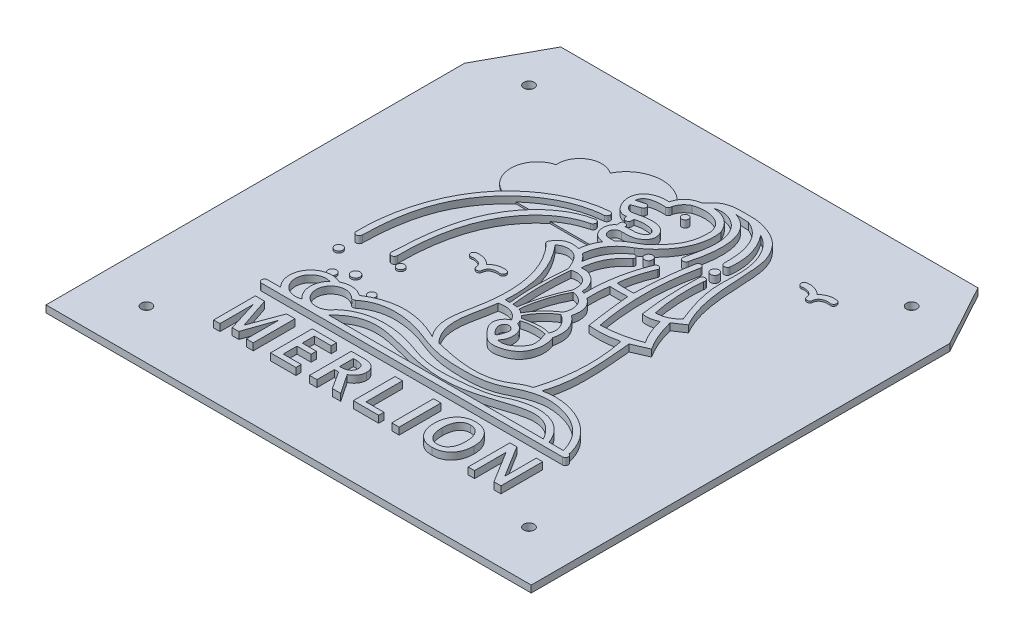
SolidWorks part; units mm, degrees
ref_plane "Front Plane" through (0, 0, 0) normal (0, 0, 1) x (1, 0, 0)
ref_plane "Top Plane" through (0, 0, 0) normal (0, 1, 0) x (1, 0, 0)
ref_plane "Right Plane" through (0, 0, 0) normal (1, 0, 0) x (0, 0, -1)
sketch "Sketch2" plane through (0, 0, 0) normal (0, 1, 0) x (1, 0, 0)
  line L0 (-69.75, 120.33) -> (-69.75, 0)
  line L1 (-69.75, 0) -> (69.75, 0)
  line L2 (69.75, 0) -> (69.75, 120.33)
  line L3 (69.75, 120.33) -> (59.98, 138.2123)
  line L4 (59.98, 138.2123) -> (-59.98, 138.2123)
  line L5 (-59.98, 138.2123) -> (-69.75, 120.33)
  line L6 (-55, 124.11) -> (-55, 14.11) construction
  line L7 (-55, 14.11) -> (55, 14.11) construction
  line L8 (55, 14.11) -> (55, 124.11) construction
  line L9 (55, 124.11) -> (-55, 124.11) construction
  line L10 (0, 14.11) -> (0, 0) construction
  circle A0 centre (-55, 124.11) radius 1.5
  circle A1 centre (55, 124.11) radius 1.5
  circle A2 centre (55, 14.11) radius 1.5
  circle A3 centre (-55, 14.11) radius 1.5
  point P6 (0, 0)
  dimension "D6" = 3
  dimension "D1" = 139.5
  dimension "D2" = 120.33
  dimension "D3" = 118.65
  dimension "D4" = 118.65
  dimension "D5" = 119.96
  dimension "D7" = 110
  dimension "D8" = 110
  dimension "D9" = 14.11
extrude "Boss-Extrude1" add sketch "Sketch2" along normal blind 2
sketch "Sketch4" plane through (0, 2, 0) normal (0, 1, 0) x (1, 0, 0)
  text T0 "BOROBUDUR" font "Lucida Sans Unicode" height 13
  point P1 (-42.6909, 27.0637)
  point P2 (-44.2843, 26.8361)
extrude "Boss-Extrude3" [suppressed] add sketch "Sketch4" along normal blind 2
sketch "Sketch7" plane through (0, 2, 0) normal (0, 1, 0) x (1, 0, 0)
  line L0 (-1201.3468, -665.5379) -> (-197.3468, -665.5379) construction
  line L1 (192.2315, 826.584) -> (1196.2315, 826.584) construction
  line L2 (44.3003, 34.3883) -> (-42.1624, 34.3883)
  line L3 (-42.1624, 36.1128) -> (-38.4101, 36.1128)
  line L4 (-24.5761, 36.1128) -> (37.1275, 36.1128)
  line L5 (38.7521, 36.1128) -> (42.84, 36.1128)
  line L6 (-3.6083, 95.618) -> (-1.8162, 95.618)
  line L7 (8.8644, 119.6853) -> (12.6966, 119.5166)
  arc A0 (-9.9574, 100.5454) -> (-10.1272, 102.3547) centre (-9.9588, 101.4579) ccw
  arc A1 (-41.4476, 60.8648) -> (-39.6862, 60.8648) centre (-40.5669, 60.8648) ccw
  arc A2 (-9.8077, 96.5277) -> (-10.1913, 98.2839) centre (-9.9451, 97.4177) ccw
  arc A3 (-31.2299, 60.8454) -> (-29.4923, 60.7921) centre (-30.3624, 60.7758) ccw
  arc A5 (-32.8244, 44.6802) -> (-32.4376, 36.2676) centre (-28.5345, 40.6623) ccw
  arc A6 (-32.8244, 44.6802) -> (-32.4376, 36.2676) centre (-34.0547, 40.4085) ccw
  arc A7 (-25.9183, 43.968) -> (-24.9659, 38.4179) centre (-28.5345, 40.6623) ccw
  arc A8 (-42.1624, 36.1128) -> (-42.1624, 34.3883) centre (-42.1624, 35.2506) ccw
  arc A9 (44.3003, 34.3883) -> (44.5437, 36.0777) centre (44.3003, 35.2506) ccw
  arc A10 (-25.0696, 45.4102) -> (-31.279, 45.8599) centre (-28.5345, 40.6623) ccw
  arc A11 (-31.279, 45.8599) -> (-38.4101, 36.1128) centre (-34.0547, 40.4085) ccw
  arc A12 (-3.128, 111.4372) -> (-2.2531, 112.4271) centre (-3.0754, 112.2722) ccw
  arc A13 (-6.7924, 109.4078) -> (-6.3281, 107.7759) centre (-6.5603, 108.5919) cw
  arc A14 (12.0547, 101.618) -> (13.7739, 101.118) centre (12.9, 101.3189) ccw
  arc A15 (19.3136, 105.971) -> (21.1274, 105.8666) centre (20.2204, 105.9169) ccw
  circle A16 centre (2.3013, 111.7181) radius 0.9837
  circle A17 centre (7.065, 96.4138) radius 1.1652
  circle A18 centre (20.2204, 102.2849) radius 1.1751
  arc A19 (5.0875, 93.854) -> (3.8629, 94.9403) centre (4.425, 94.3406) ccw
  arc A20 (11.2355, 94.4528) -> (9.7612, 95.2234) centre (10.5518, 94.9403) ccw
  arc A21 (17.1346, 101.1863) -> (15.4382, 101.5027) centre (16.2926, 101.3778) ccw
  arc A22 (20.9973, 98.2839) -> (19.3636, 98.6157) centre (20.2204, 98.6465) ccw
  spline S0 degree 3 poles (-9.9588, 102.3704) (-18.6465, 101.5875) (-36.2323, 91.1471) (-41.6505, 71.1239) (-41.4476, 60.8648) knots 0 0 0 0 0.451584 1 1 1 1
  spline S1 degree 3 poles (-39.6862, 60.8648) (-39.5972, 67.3837) (-37.455, 85.8607) (-21.5995, 99.5998) (-9.8077, 100.558) knots 0 0 0 0 0.362724 1 1 1 1
  spline S2 degree 3 poles (-31.2327, 60.7758) (-30.8994, 69.13) (-29.556, 85.1596) (-17.0075, 96.9409) (-10.1913, 98.2839) knots 0 0 0 0 0.551911 1 1 1 1
  spline S3 degree 3 poles (-9.8077, 96.5277) (-16.2307, 94.9492) (-27.5198, 84.0891) (-29.568, 68.812) (-29.4922, 60.7758) knots 0 0 0 0 0.442158 1 1 1 1
  spline S4 degree 3 poles (-26.0695, 37.2424) (-21.5331, 42.7418) (-12.2233, 43.2325) (0.2095, 38.4079) (5.0793, 37.912) (21.0184, 39.3159) (20.0588, 41.0511) (31.0608, 43.7308) (36.8095, 41.5293) (38.7521, 36.1128) knots 0 0 0 0 0.209239 0.240528 0.334429 0.377612 0.660626 0.719916 1 1 1 1
  spline S5 degree 3 poles (-24.5761, 36.1128) (-22.9325, 37.9529) (-17.4081, 41.5272) (-7.6539, 39.3095) (1.9661, 36.5213) (12.7707, 36.1717) (24.3192, 40.3392) (33.3882, 42.7039) (37.1275, 36.1128) knots 0 0 0 0 0.115498 0.281888 0.432798 0.585218 0.767439 1 1 1 1
  spline S6 degree 2 poles (-25.0696, 45.4102) (-15.7624, 51.4204) (-4.3446, 45.6251) knots 0 0 0 1 1 1
  spline S7 degree 3 poles (-4.3446, 45.6251) (-8.0002, 50.3018) (-3.2731, 63.7943) (-4.6708, 78.3512) (-10.9267, 84.9324) knots 0 0 0 0 0.374184 1 1 1 1
  spline S8 degree 2 poles (-10.9267, 84.9324) (-11.6464, 85.2936) (-11.3916, 86.0741) knots 0 0 0 1 1 1
  spline S9 degree 2 poles (-11.3916, 86.0741) (-9.5366, 89.6845) (-5.21, 88.5802) knots 0 0 0 1 1 1
  spline S10 degree 2 poles (-3.4433, 93.735) (-4.9873, 91.3749) (-5.21, 88.5802) knots 0 0 0 1 1 1
  spline S11 degree 3 poles (-5.597, 100.0006) (-7.2855, 98.9493) (-7.2984, 94.7473) (-4.3168, 93.8483) (-3.4433, 93.735) knots 0 0 0 0 0.6762 1 1 1 1
  spline S12 degree 2 poles (-25.9183, 43.968) (-25.2496, 43.1673) (-24.4072, 43.6465) knots 0 0 0 1 1 1
  spline S13 degree 3 poles (-24.4072, 43.6465) (-22.0022, 45.6472) (-16.1415, 47.2243) (-6.3264, 45.027) (-0.4952, 41.8053) (15.7146, 41.4602) (19.5224, 44.5582) (26.0491, 46.7407) (32.7571, 46.4087) (40.8745, 43.8715) (42.84, 36.1128) knots 0 0 0 0 0.133923 0.258154 0.412619 0.501567 0.692749 0.812953 0.843678 1 1 1 1
  spline S14 degree 3 poles (-5.597, 100.0006) (-5.704, 100.3924) (-5.9698, 102.1171) (-3.8284, 101.5488) (-3.9822, 100.7065) knots 0 0 0 0 0.434244 1 1 1 1
  spline S15 degree 3 poles (-3.9822, 100.7065) (-2.6514, 100.9332) (-0.0463, 100.2599) (2.3348, 102.8556) (0.3378, 103.948) knots 0 0 0 0 0.520536 1 1 1 1
  spline S16 degree 2 poles (0.3378, 103.948) (-2.075, 104.5253) (-4.5507, 103.8172) knots 0 0 0 1 1 1
  spline S17 degree 3 poles (-6.3281, 103.5013) (-6.4115, 103.013) (-5.8594, 102.057) (-4.4292, 102.476) (-4.4559, 103.4081) (-4.5507, 103.8172) knots 0 0 0 0 0.417961 0.636874 1 1 1 1
  spline S18 degree 3 poles (-6.3281, 103.5013) (-8.4367, 102.9694) (-11.2774, 106.4974) (-10.2348, 112.4129) (-5.8343, 113.4739) (-3.8248, 113.1894) knots 0 0 0 0 0.371124 0.593458 1 1 1 1
  spline S19 degree 2 poles (-3.8248, 113.1894) (-2.8716, 117.0541) (1.2989, 117.681) knots 0 0 0 1 1 1
  spline S20 degree 3 poles (1.2989, 117.681) (3.1476, 119.8951) (5.116, 121.6799) (12.1692, 121.2827) (12.2063, 121.2856) knots 0 0 0 0 0.585988 1 1 1 1
  spline S21 degree 3 poles (12.2063, 121.2856) (13.5142, 121.3862) (20.9862, 119.7893) (24.7521, 113.4441) (25.7161, 101.2762) (25.5312, 92.4052) (29.5848, 85.3724) knots 0 0 0 0 0.163326 0.384304 0.482541 1 1 1 1
  spline S22 degree 1 poles (29.5848, 85.3724) (26.4274, 83.2732) knots 0 0 1 1
  spline S23 degree 2 poles (26.4274, 83.2732) (27.5746, 78.3368) (30.2933, 74.0449) knots 0 0 0 1 1 1
  spline S24 degree 1 poles (30.2933, 74.0449) (25.7936, 72.0858) knots 0 0 1 1
  spline S25 degree 3 poles (25.7936, 72.0858) (26.4016, 64.0995) (27.6462, 55.6264) (24.9599, 47.872) knots 0 0 0 0 1 1 1 1
  spline S26 degree 3 poles (24.9599, 47.872) (33.0759, 49.8059) (42.8659, 44.8291) (44.5437, 36.0777) knots 0 0 0 0 1 1 1 1
  spline S27 degree 3 poles (-3.1859, 63.4282) (-3.9284, 57.2074) (-7.1533, 50.844) (-1.8192, 44.9976) knots 0 0 0 0 1 1 1 1
  spline S28 degree 3 poles (-1.8192, 44.9976) (4.1645, 43.5344) (14.1995, 41.3944) (20.8906, 47.1117) (22.8204, 47.4385) knots 0 0 0 0 0.776426 1 1 1 1
  spline S29 degree 2 poles (23.9973, 71.5121) (26.5843, 59.2972) (22.8204, 47.4385) knots 0 0 0 1 1 1
  spline S30 degree 2 poles (23.9973, 71.5121) (19.749, 70.5578) (15.4112, 70.9169) knots 0 0 0 1 1 1
  spline S31 degree 2 poles (13.8106, 83.688) (14.3724, 77.2732) (15.4112, 70.9169) knots 0 0 0 1 1 1
  spline S32 degree 2 poles (13.8106, 83.688) (11.2436, 83.5727) (8.6755, 83.6547) knots 0 0 0 1 1 1
  spline S33 degree 2 poles (8.6755, 83.6547) (8.266, 80.5313) (8.3823, 77.3858) knots 0 0 0 1 1 1
  spline S34 degree 2 poles (8.3823, 77.3858) (11.631, 75.0661) (10.4094, 70.9169) knots 0 0 0 1 1 1
  spline S35 degree 2 poles (10.4094, 70.9169) (14.4782, 67.7465) (13.2535, 62.6732) knots 0 0 0 1 1 1
  spline S36 degree 3 poles (13.2535, 62.6732) (14.3855, 60.146) (13.7097, 54.8964) (8.1479, 52.1397) (4.8247, 52.0734) (3.5735, 53.5294) knots 0 0 0 0 0.480478 0.711461 1 1 1 1
  spline S37 degree 2 poles (-3.1859, 63.4282) (1.021, 64.3573) (2.9328, 61.1538) knots 0 0 0 1 1 1
  spline S38 degree 3 poles (2.9328, 61.1538) (1.6183, 60.672) (-0.5797, 57.2938) (2.4911, 54.5357) (3.5735, 53.5294) knots 0 0 0 0 0.449877 1 1 1 1
  spline S39 degree 3 poles (5.2054, 57.0106) (4.4437, 54.5831) (2.9327, 56.5403) (2.1551, 58.1418) (3.6032, 59.7885) (5.6321, 58.8238) (5.2054, 57.0106) (4.4437, 54.5831) (2.9327, 56.5403) knots -0.521404 -0.356772 -0.182723 0 0.123715 0.355045 0.478596 0.643228 0.817277 1 1.123715 1.355045 1.478596 only from (4.2168, 55.232) to (4.2168, 55.232)
  spline S40 degree 2 poles (-2.9936, 65.2803) (-2.3418, 65.2822) (-1.69, 65.2738) knots 0 0 0 1 1 1
  spline S41 degree 2 poles (-1.69, 65.2738) (-2.5999, 73.6639) (-1.694, 82.0912) knots 0 0 0 1 1 1
  spline S42 degree 3 poles (-9.4419, 86.0741) (-8.2016, 87.3778) (-3.8051, 87.4453) (-2.3241, 83.6079) (-1.694, 82.0912) knots 0 0 0 0 0.491916 1 1 1 1
  spline S43 degree 2 poles (-9.4419, 86.0741) (-2.1212, 77.5216) (-2.9936, 65.2803) knots 0 0 0 1 1 1
  spline S44 degree 3 poles (-0.8871, 82.0912) (0.5776, 82.7015) (4.1583, 81.7892) (4.3528, 78.5088) (4.2168, 77.3858) knots 0 0 0 0 0.574295 1 1 1 1
  spline S45 degree 2 poles (4.2168, 77.3858) (1.4329, 71.5479) (0.4533, 65.1751) knots 0 0 0 1 1 1
  spline S46 degree 2 poles (0.4533, 65.1751) (-0.1584, 65.3231) (-0.7859, 65.2738) knots 0 0 0 1 1 1
  spline S47 degree 2 poles (-0.8871, 82.0912) (-1.7443, 73.6867) (-0.7859, 65.2738) knots 0 0 0 1 1 1
  spline S48 degree 3 poles (4.854, 76.8797) (5.0166, 77.0771) (9.1263, 75.9903) (9.0408, 71.8604) (8.3823, 70.5218) knots 0 0 0 0 0.519773 1 1 1 1
  spline S49 degree 2 poles (4.854, 76.8797) (1.8606, 71.3103) (1.2989, 64.9239) knots 0 0 0 1 1 1
  spline S50 degree 2 poles (1.2989, 64.9239) (1.9566, 64.7121) (2.4616, 64.2464) knots 0 0 0 1 1 1
  spline S51 degree 2 poles (2.4616, 64.2464) (4.638, 68.1328) (8.3823, 70.5218) knots 0 0 0 1 1 1
  spline S52 degree 2 poles (3.2861, 63.7169) (3.6412, 63.4141) (3.8629, 63.0013) knots 0 0 0 1 1 1
  spline S53 degree 2 poles (3.2861, 63.7169) (5.1268, 67.4166) (8.6755, 69.6202) knots 0 0 0 1 1 1
  spline S54 degree 3 poles (8.6755, 69.6202) (10.7389, 68.3853) (12.7351, 65.7874) (11.5328, 63.2745) knots 0 0 0 0 1 1 1 1
  spline S55 degree 3 poles (3.8629, 63.0013) (6.3753, 63.4447) (9.0203, 64.2124) (11.5328, 63.2745) knots 0 0 0 0 1 1 1 1
  spline S56 degree 2 poles (4.3163, 62.2065) (4.6107, 61.6696) (4.7372, 61.0701) knots 0 0 0 1 1 1
  spline S57 degree 3 poles (4.7372, 61.0701) (7.5196, 60.4003) (7.9025, 56.0031) (5.8745, 54.2372) knots 0 0 0 0 1 1 1 1
  spline S58 degree 2 poles (4.3163, 62.2065) (7.7471, 63.2407) (11.2659, 62.4876) knots 0 0 0 1 1 1
  spline S59 degree 3 poles (11.2659, 62.4876) (11.7235, 61.1356) (12.7693, 58.42) (10.0449, 55.0325) (7.7135, 53.6534) (5.8745, 54.2372) knots 0 0 0 0 0.376185 0.582397 1 1 1 1
  spline S60 degree 3 poles (-9.0468, 108.7664) (-8.9076, 111.493) (-5.0389, 111.5177) (-3.128, 111.4372) knots 0 0 0 0 1 1 1 1
  spline S61 degree 2 poles (-2.2531, 112.4271) (-1.6986, 114.5235) (0.3378, 115.6368) knots 0 0 0 1 1 1
  spline S62 degree 3 poles (0.3378, 115.6368) (3.7295, 116.8046) (8.8984, 116.2484) (9.6129, 111.7181) knots 0 0 0 0 1 1 1 1
  spline S63 degree 3 poles (-1.8162, 95.618) (-0.0135, 97.9379) (3.256, 98.2712) (4.854, 100.7992) knots 0 0 0 0 1 1 1 1
  spline S64 degree 2 poles (9.6129, 111.7181) (9.96, 105.1658) (4.854, 100.7992) knots 0 0 0 1 1 1
  spline S65 degree 1 poles (-9.0468, 108.7664) (-6.7924, 109.4078) knots 0 0 1 1
  spline S66 degree 1 poles (-6.3281, 107.7759) (-8.7686, 106.8923) knots 0 0 1 1
  spline S67 degree 2 poles (-8.7686, 106.8923) (-8.2897, 105.2926) (-6.5603, 105.237) knots 0 0 0 1 1 1
  spline S68 degree 3 poles (-6.5603, 105.237) (-4.3865, 105.8051) (-0.6609, 106.5981) (2.753, 104.8536) (3.3691, 101.6215) (0.7935, 99.0359) (-0.8998, 98.969) (-3.2955, 98.946) knots 0 0 0 0 0.331805 0.515953 0.641551 0.744836 1 1 1 1
  spline S69 degree 3 poles (-3.2955, 98.946) (-4.1537, 99.0447) (-6.0426, 97.5159) (-4.6017, 95.587) (-3.6083, 95.618) knots 0 0 0 0 0.499483 1 1 1 1
  spline S70 degree 2 poles (-3.4433, 87.8983) (-2.8002, 93.9106) (2.6453, 96.76) knots 0 0 0 1 1 1
  spline S71 degree 3 poles (2.6453, 96.76) (7.967, 100.0682) (12.3862, 106.7228) (11.1166, 113.1894) knots 0 0 0 0 1 1 1 1
  spline S72 degree 2 poles (11.1166, 113.1894) (9.1168, 117.85) (4.2168, 118.0226) knots 0 0 0 1 1 1
  spline S73 degree 3 poles (4.2168, 118.0226) (6.5836, 118.9067) (10.5555, 117.6101) (14.3986, 110.9172) (12.819, 105.2946) (12.0547, 101.618) knots 0 0 0 0 0.329991 0.465743 1 1 1 1
  spline S74 degree 3 poles (13.7739, 101.118) (15.4646, 107.1013) (16.8745, 117.1203) (8.8644, 119.6853) knots 0 0 0 0 1 1 1 1
  spline S75 degree 3 poles (12.6966, 119.5166) (18.8625, 117.0606) (19.4394, 110.0745) (19.312, 105.9169) knots 0 0 0 0 1 1 1 1
  spline S76 degree 2 poles (17.7316, 118.0226) (21.886, 112.6202) (21.1167, 105.7691) knots 0 0 0 1 1 1
  spline S77 degree 2 poles (-3.4433, 87.8983) (-2.2699, 87.0497) (-1.538, 85.7899) knots 0 0 0 1 1 1
  spline S78 degree 2 poles (-1.538, 85.7899) (-0.7653, 91.6045) (3.8629, 94.9403) knots 0 0 0 1 1 1
  spline S79 degree 2 poles (5.0875, 93.854) (0.4024, 90.2001) (-0.0465, 84.1287) knots 0 0 0 1 1 1
  spline S80 degree 3 poles (-0.0465, 84.1287) (3.0035, 84.8327) (6.2448, 81.5319) (5.8745, 78.5091) knots 0 0 0 0 1 1 1 1
  spline S81 degree 1 poles (5.8745, 78.5091) (6.6716, 78.2195) knots 0 0 1 1
  spline S82 degree 2 poles (6.6716, 78.2195) (6.4617, 87.0746) (9.7864, 95.2859) knots 0 0 0 1 1 1
  spline S83 degree 2 poles (11.3755, 94.7768) (9.4301, 90.3396) (8.9086, 85.5298) knots 0 0 0 1 1 1
  spline S84 degree 2 poles (8.9086, 85.5298) (11.3546, 85.2949) (13.8106, 85.3724) knots 0 0 0 1 1 1
  spline S85 degree 2 poles (13.8106, 85.3724) (13.9069, 93.5141) (15.4382, 101.5027) knots 0 0 0 1 1 1
  spline S86 degree 2 poles (17.1389, 101.2059) (14.0983, 87.0904) (16.9583, 72.604) knots 0 0 0 1 1 1
  spline S87 degree 2 poles (16.9583, 72.604) (22.5437, 72.7989) (27.7991, 74.7477) knots 0 0 0 1 1 1
  spline S88 degree 2 poles (24.6924, 82.1781) (25.5052, 78.1579) (27.7991, 74.7477) knots 0 0 0 1 1 1
  spline S89 degree 2 poles (19.3697, 98.7534) (18.9772, 90.0839) (20.2204, 81.4905) knots 0 0 0 1 1 1
  spline S90 degree 2 poles (24.6924, 82.1781) (22.5972, 81.0423) (20.2204, 81.4905) knots 0 0 0 1 1 1
  spline S91 degree 3 poles (17.7316, 118.0226) (21.8789, 115.8395) (24.7844, 108.5177) (23.2658, 97.0313) (25.7972, 90.0476) (27.3485, 86.0741) knots 0 0 0 0 0.382795 0.621776 1 1 1 1
  spline S92 degree 2 poles (20.9973, 98.2839) (20.2874, 90.9024) (21.8373, 83.6214) knots 0 0 0 1 1 1
  spline S93 degree 2 poles (21.8373, 83.6214) (25.0898, 83.6405) (27.3485, 86.0741) knots 0 0 0 1 1 1
  point P317 (0, 0)
  point P325 (21.8373, 83.688)
extrude "Boss-Extrude7" add sketch "Sketch7" along normal blind 2 contours A1 S1 A0 S0 | S3 A2 S2 A3 | S26 S25 S24 S23 S22 S21 S20 S19 S18 S17 S16 S15 S14 S11 S10 S9 S8 S7 S6 A10 A11 L3 A8 L2 A9 S93 S92 A22 S89 S90 S88 S87 S86 A21 S85 S84 S83 A20 S82 S81 S80 S79 A19 S78 S77 S70 | A16 | A17 | A18 region at (1.0689, 2, -35.6268) region at (-32.9879, 2, -87.0752) region at (-25.9576, 2, -82.4267) region at (2.3013, 2, -111.7181) region at (7.065, 2, -96.4138) region at (20.2204, 2, -102.2849)
sketch "Sketch8" plane through (0, 2, 0) normal (0, 1, 0) x (1, 0, 0)
  line L0 (-4.0509, 92.6907) -> (-17.5279, 92.6907)
  line L1 (-17.5279, 92.6907) -> (-28.2739, 92.6907)
  line L2 (-4.0509, 92.6907) -> (-2.0037, 94.7379)
  line L3 (-2.0037, 94.7379) -> (-5.8135, 95.2563)
  line L4 (-5.8135, 95.2563) -> (-5.8135, 98.278)
  line L5 (-5.8135, 98.278) -> (-3.9086, 99.7889)
  line L6 (-3.9086, 99.7889) -> (1.309, 100.3393)
  line L7 (1.309, 100.3393) -> (2.1184, 102.7027)
  line L8 (2.1184, 102.7027) -> (1.1105, 104.7605)
  line L9 (1.1105, 104.7605) -> (-5.3819, 104.7605)
  line L10 (-5.3819, 104.7605) -> (-8.4575, 104.7605)
  line L11 (-8.4575, 104.7605) -> (-9.7601, 107.4198)
  line L12 (-9.7601, 107.4198) -> (-9.7601, 110.4188)
  line L13 (-9.7601, 110.4188) -> (-3.0273, 112.6311)
  line L14 (-3.2257, 114.7782) -> (-3.0273, 112.6311)
  line L15 (-16.0108, 72.9703) -> (-16.0108, 70.0217) construction
  arc A0 (-30.8316, 107.7396) -> (-28.2739, 92.6907) centre (-28.8221, 100.3393) ccw
  arc A7 (-3.2257, 114.7782) -> (-20.9425, 113.4284) centre (-11.675, 108.7338) ccw
  arc A8 (-20.9425, 113.4284) -> (-30.8316, 107.7396) centre (-24.5118, 108.1935) ccw
  arc A12 (-16.8919, 70.9027) -> (-15.1298, 70.9027) centre (-16.0108, 70.9027) ccw
  arc A13 (-20.4261, 74.3359) -> (-20.0168, 72.5989) centre (-20.2215, 73.4674) ccw
  arc A14 (-11.5955, 74.3359) -> (-12.0049, 72.5989) centre (-11.8002, 73.4674) cw
  arc A18 (34.5739, 114.3359) -> (34.9832, 112.5989) centre (34.7785, 113.4674) ccw
  arc A19 (38.1081, 110.9027) -> (39.8702, 110.9027) centre (38.9892, 110.9027) ccw
  arc A20 (43.4045, 114.3359) -> (42.9951, 112.5989) centre (43.1998, 113.4674) cw
  arc A24 (-21.1108, 113.5393) -> (-20.0168, 112.5989) centre (-20.2215, 113.4674) ccw [skipped]
  arc A25 (-16.8919, 110.9027) -> (-15.1298, 110.9027) centre (-16.0108, 110.9027) ccw [skipped]
  arc A26 (-11.5955, 114.3359) -> (-12.0049, 112.5989) centre (-11.8002, 113.4674) cw [skipped]
  arc A27 (43.4045, 74.3359) -> (42.9951, 72.5989) centre (43.1998, 73.4674) cw [skipped]
  arc A28 (38.1081, 70.9027) -> (39.8702, 70.9027) centre (38.9892, 70.9027) ccw [skipped]
  arc A29 (34.5739, 74.3359) -> (34.9832, 72.5989) centre (34.7785, 73.4674) ccw [skipped]
  circle A30 centre (-27.7919, 60.0193) radius 1.1053
  circle A31 centre (-41.3903, 55.7991) radius 1.1665
  circle A32 centre (-36.246, 48.8001) radius 1.1878
  circle A33 centre (-32.3339, 51.5906) radius 1.2718
  circle A34 centre (-24.8927, 48.8001) radius 1.1028
  parabola Q0 (-3.4433, 93.735) -> (-5.21, 88.5802) focus (0.3698, 89.4739) apex (-4.6988, 91.1416) construction
  parabola Q1 (-3.8248, 113.1894) -> (1.2989, 117.681) focus (-0.5136, 114.2316) apex (-2.299, 116.0284) construction
  spline S0 degree 3 poles (-9.8077, 96.5277) (-16.2307, 94.9492) (-27.5198, 84.0891) (-29.568, 68.812) (-29.4922, 60.7758) knots 0 0 0 0 0.442158 1 1 1 1 construction
  spline S1 degree 2 poles (-20.4261, 74.3359) (-17.9694, 74.7361) (-16.0108, 72.9703) knots 0 0 0 1 1 1
  spline S2 degree 3 poles (-20.0168, 72.5989) (-19.7381, 72.6646) (-18.3587, 72.6912) (-17.0562, 72.0801) (-16.8919, 70.9027) knots 0 0 0 0 0.236952 1 1 1 1
  spline S3 degree 3 poles (-12.0049, 72.5989) (-12.2836, 72.6646) (-13.663, 72.6912) (-14.9655, 72.0801) (-15.1298, 70.9027) knots 0 0 0 0 0.236952 1 1 1 1
  spline S4 degree 2 poles (-11.5955, 74.3359) (-14.0523, 74.7361) (-16.0108, 72.9703) knots 0 0 0 1 1 1
  spline S9 degree 2 poles (34.5739, 114.3359) (37.0306, 114.7361) (38.9892, 112.9703) knots 0 0 0 1 1 1
  spline S10 degree 3 poles (34.9832, 112.5989) (35.2619, 112.6646) (36.6413, 112.6912) (37.9438, 112.0801) (38.1081, 110.9027) knots 0 0 0 0 0.236952 1 1 1 1
  spline S11 degree 3 poles (42.9951, 112.5989) (42.7164, 112.6646) (41.337, 112.6912) (40.0345, 112.0801) (39.8702, 110.9027) knots 0 0 0 0 0.236952 1 1 1 1
  spline S12 degree 2 poles (43.4045, 114.3359) (40.9477, 114.7361) (38.9892, 112.9703) knots 0 0 0 1 1 1
  spline S13 degree 2 poles (-20.4261, 114.3359) (-20.4249, 114.3361) (-20.4237, 114.3363) knots 0 0 0 0.000503 0.000503 0.000503
  spline M30 degree 2 poles (-5.21, 88.5802) (-4.9873, 91.3749) (-3.4433, 93.735) knots 0 0 0 1 1 1
  spline M31 degree 3 poles (-3.4433, 93.735) (-4.3168, 93.8483) (-7.2984, 94.7473) (-7.2855, 98.9493) (-5.597, 100.0006) knots 0 0 0 0 0.3238 1 1 1 1
  spline M32 degree 3 poles (-5.597, 100.0006) (-5.704, 100.3924) (-5.9698, 102.1171) (-3.8284, 101.5488) (-3.9822, 100.7065) knots 0 0 0 0 0.434244 1 1 1 1
  spline M33 degree 3 poles (-3.9822, 100.7065) (-2.6514, 100.9332) (-0.0463, 100.2599) (2.3348, 102.8556) (0.3378, 103.948) knots 0 0 0 0 0.520536 1 1 1 1
  spline M34 degree 2 poles (0.3378, 103.948) (-2.075, 104.5253) (-4.5507, 103.8172) knots 0 0 0 1 1 1
  spline M35 degree 3 poles (-4.5507, 103.8172) (-4.4559, 103.4081) (-4.4292, 102.476) (-5.8594, 102.057) (-6.4115, 103.013) (-6.3281, 103.5013) knots 0 0 0 0 0.363126 0.582039 1 1 1 1
  spline M36 degree 3 poles (-6.3281, 103.5013) (-8.4367, 102.9694) (-11.2774, 106.4974) (-10.2348, 112.4129) (-5.8343, 113.4739) (-3.8248, 113.1894) knots 0 0 0 0 0.371124 0.593458 1 1 1 1
  spline M37 degree 2 poles (-3.8248, 113.1894) (-2.8716, 117.0541) (1.2989, 117.681) knots 0 0 0 1 1 1
  spline M44 degree 3 poles (-9.8077, 100.558) (-21.5995, 99.5998) (-37.455, 85.8607) (-39.5972, 67.3837) (-39.6862, 60.8648) knots 0 0 0 0 0.637276 1 1 1 1
  spline M46 degree 3 poles (-41.4476, 60.8648) (-41.6505, 71.1239) (-36.2323, 91.1471) (-18.6465, 101.5875) (-9.9588, 102.3704) knots 0 0 0 0 0.548416 1 1 1 1
  arc M47 (-9.9588, 102.3704) -> (-9.8077, 100.558) centre (-9.9588, 101.4579) cw
  spline M58 degree 3 poles (-9.8077, 96.5277) (-16.2307, 94.9492) (-27.5198, 84.0891) (-29.568, 68.812) (-29.4922, 60.7758) knots 0 0 0 0 0.442158 1 1 1 1
  spline M60 degree 3 poles (-31.2327, 60.7758) (-30.8994, 69.13) (-29.556, 85.1596) (-17.0075, 96.9409) (-10.1913, 98.2839) knots 0 0 0 0 0.551911 1 1 1 1
  arc M61 (-10.1913, 98.2839) -> (-9.8077, 96.5277) centre (-9.9451, 97.4177) cw
  dimension "D1" = 2
  dimension "D2" = 2
extrude "Boss-Extrude8" add sketch "Sketch8" along normal blind 0.5 from surface contours A7 A8 A0 L1 L0 M46 M47 M44 M60 M61 M58 M30 M31 M32 M33 M34 M35 M36 M37 | A20 S12 S9 A18 S10 A19 S11 | L15 S1 A13 S2 A12 | S4 L15 A12 S3 A14 | A31 | A33 | A30 | A34 | A32 region at (-19.291, 2, -104.6797) region at (-13.8197, 2, -72.8813) region at (-18.202, 2, -72.8813) region at (38.9892, 2, -112.8813) region at (-27.7919, 2, -60.0193) region at (-41.3903, 2, -55.7991) region at (-36.246, 2, -48.8001) region at (-32.3339, 2, -51.5906) region at (-24.8927, 2, -48.8001) starting at face at (-1.758, 2, -76.4654)
sketch "Sketch9" plane through (0, 2, 0) normal (0, 1, 0) x (1, 0, 0)
  text T0 "MERLION" font "Lucida Sans Unicode" height 12
extrude "Boss-Extrude9" add sketch "Sketch9" along normal blind 2
